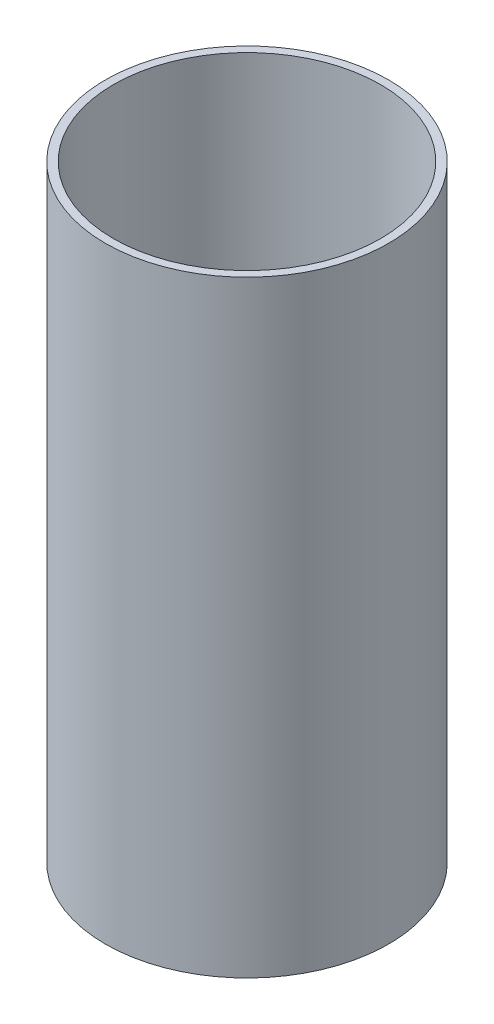
SolidWorks part; units mm, degrees
material "AISI 304"
ref_plane "Спереди" through (0, 0, 0) normal (0, 0, 1) x (1, 0, 0)
ref_plane "Сверху" through (0, 0, 0) normal (0, 1, 0) x (1, 0, 0)
ref_plane "Справа" through (0, 0, 0) normal (1, 0, 0) x (0, 0, -1)
ref_axis "ОсьX" through (-88.99, 0, 0) along (1, 0, 0)
ref_axis "ОсьZ" through (0, 55, 0) along (0, -1, 0)
ref_axis "ОсьY" through (0, 0, -88.99) along (0, 0, 1)
sketch "Эскиз1" plane through (0, 0, 0) normal (0, 0, 1) x (1, 0, 0)
  line L0 (-70, 300) -> (-70, 0)
  line L1 (0, 26.169) -> (0, -22.1581) construction
  dimension "D1" = 140
  dimension "D2" = 300
revolve "Повернуть-Тонкостенный1" add sketch "Эскиз1" angle 360 about L1 wall 4
